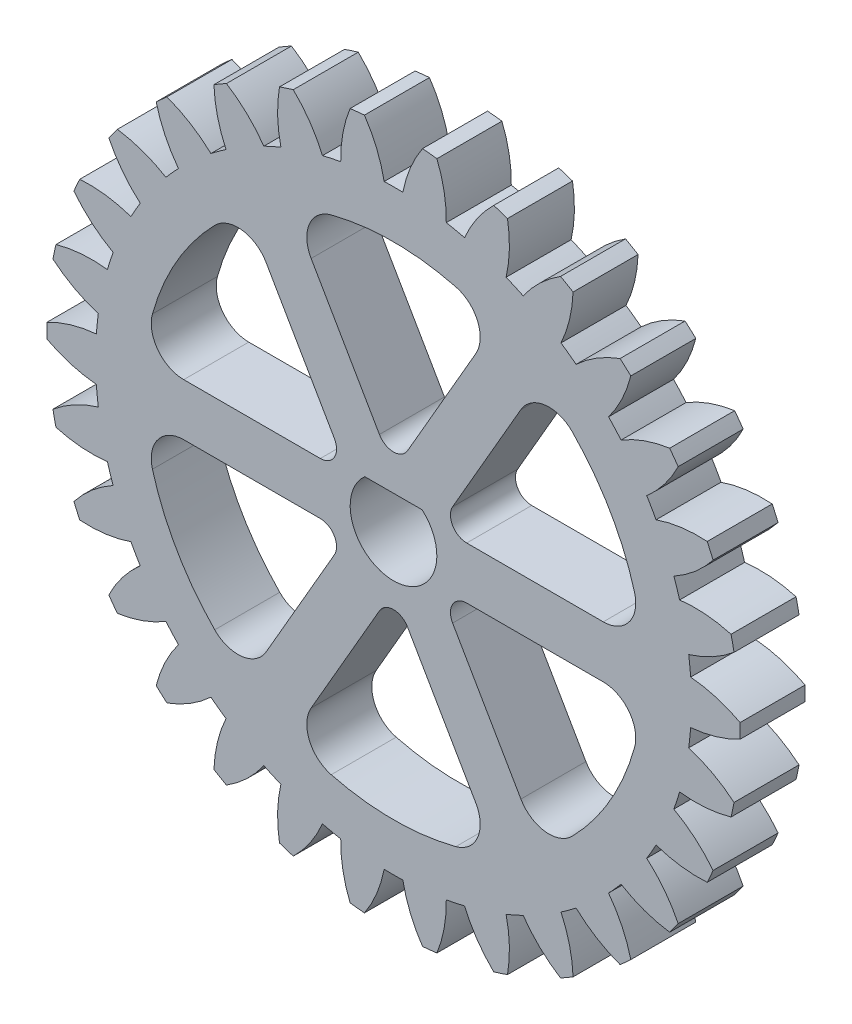
SolidWorks part; units mm, degrees
ref_plane "Front Plane" through (0, 0, 0) normal (0, 0, 1) x (1, 0, 0)
ref_plane "Top Plane" through (0, 0, 0) normal (0, 1, 0) x (1, 0, 0)
ref_plane "Right Plane" through (0, 0, 0) normal (1, 0, 0) x (0, 0, -1)
sketch "Sketch1" plane through (0, 0, 0) normal (0, 0, 1) x (1, 0, 0)
  circle A0 centre (0, 0) radius 16
  dimension "addendumDiameter " = 32
extrude "Boss-Extrude1" add sketch "Sketch1" along normal blind 3
sketch "Sketch2" plane through (0, 0, 3) normal (0, 0, 1) x (1, 0, 0)
  line L0 (0, 0) -> (0, 31.2008) construction
  line L1 (0, 0) -> (-2.5588, 24.3457) construction
  line L2 (-0.7752, 14.8891) -> (-1.5563, 14.807) construction
  circle A0 centre (0, 0) radius 13.75 construction
  circle A1 centre (0, 0) radius 14.0954 construction
  circle A2 centre (0, 0) radius 15 construction
  arc A3 (-1.3398, 15.9438) -> (-0.431, 13.7432) centre (-6.3208, 12.5987) cw
  arc A4 (-1.3398, 15.9438) -> (1.3398, 15.9438) centre (0, 0) cw
  arc A5 (-0.431, 13.7432) -> (0.431, 13.7432) centre (0, 0) cw
  circle A6 centre (0, 0) radius 16 construction
  arc A7 (1.3398, 15.9438) -> (0.431, 13.7432) centre (6.3208, 12.5987) ccw
  dimension "dedendumCircle" = 27.5
  dimension "baseDiameter" = 28.1908
  dimension "pitchDiameter" = 30
  dimension "D2" = 6
  dimension "D1" = 6
  dimension "D3" = 0.7854
extrude "Cut-Extrude1" cut sketch "Sketch2" against normal through all
pattern_circular "CirPattern1" count 30 over 360 about axis through (0, 0, 3) along (0, 0, 1) of "Cut-Extrude1"
sketch "Sketch3" plane through (0, 0, 3) normal (0, 0, 1) x (1, 0, 0)
  line L0 (0, 0) -> (-35.4164, 0) construction
  line L1 (0, 0) -> (-16.4465, 28.4861) construction
  line L5 (-3.3775, 1.2) -> (-9.6805, 1.2)
  line L6 (-2.728, 2.325) -> (-5.8795, 7.7836)
  arc A1 (-11.1254, 3.103) -> (-8.25, 8.0834) centre (0, 0) cw
  arc A2 (-5.8795, 7.7836) -> (-8.25, 8.0834) centre (-7.1785, 7.0336) ccw
  circle A3 centre (0, 0) radius 11.55 construction
  arc A4 (-9.6805, 1.2) -> (-11.1254, 3.103) centre (-9.6805, 2.7) cw
  arc A5 (-3.3775, 1.2) -> (-2.728, 2.325) centre (-3.3775, 1.95) ccw
  point P10 (-6.783, 9.3485)
  point P14 (-11.4875, 1.2)
  dimension "D5" = 23.1
  dimension "D3" = 1.5
  dimension "D4" = 0.75
  dimension "D1" = 60
  dimension "D2" = 1.2
extrude "Cut-Extrude3" cut sketch "Sketch3" against normal through all
pattern_circular "CirPattern2" count 6 over 360 about axis through (0, 0, 3) along (0, 0, -1) of "Cut-Extrude3"
sketch "Sketch4" plane through (0, 0, 3) normal (0, 0, 1) x (1, 0, 0)
  line L0 (-1.3229, 1.5) -> (1.3229, 1.5)
  line L1 (1.65, 0) -> (-1.65, 0) construction
  arc A0 (-1.3229, 1.5) -> (1.3229, 1.5) centre (0, 0) ccw
  dimension "D1" = 2
  dimension "D2" = 1.5
extrude "Cut-Extrude4" cut sketch "Sketch4" against normal through all
equation "\"module\" = 1.0"
equation "\"teeth\" = 30"
equation "\"pressureAngle\"= 20deg"
equation "\"gearThickness\"= 3"
equation "\"addendumFactor\"= 1"
equation "\"dedendumFactor\"= 1.25"
equation "\"pitch\"= 1/\"module\""
equation "\"pitchDiameter\"= \"teeth\" / \"pitch\""
equation "\"addendum\"= \"addendumFactor\" / \"pitch\""
equation "\"dedendum\"= \"dedendumFactor\" / \"pitch\""
equation "\"addendumDiameter @Sketch1\"= \"pitchDiameter\" + 2 * \"addendum\""
equation "\"D1@Boss-Extrude1\"= \"gearThickness\""
equation "\"dedendumCircle@Sketch2\" = \"pitchDiameter\" - 2 * \"dedendum\""
equation "\"baseDiameter@Sketch2\"=\"pitchDiameter\" * cos ( \"pressureAngle\" )"
equation "\"pitchDiameter@Sketch2\"=\"pitchDiameter\""
equation "\"D1@Sketch2\"=180/\"teeth\""
equation "\"D2@Sketch2\"=\"pitchDiameter\"/5"
equation "\"D3@Sketch2\"=PI / 2 / \"pitch\" / 2"
equation "\"D1@CirPattern1\"=\"teeth\""
equation "\"D5@Sketch3\"=\"pitchDiameter\"*.77"
equation "\"D2@Sketch3\"=\"module\"*\"teeth\"*.04"
